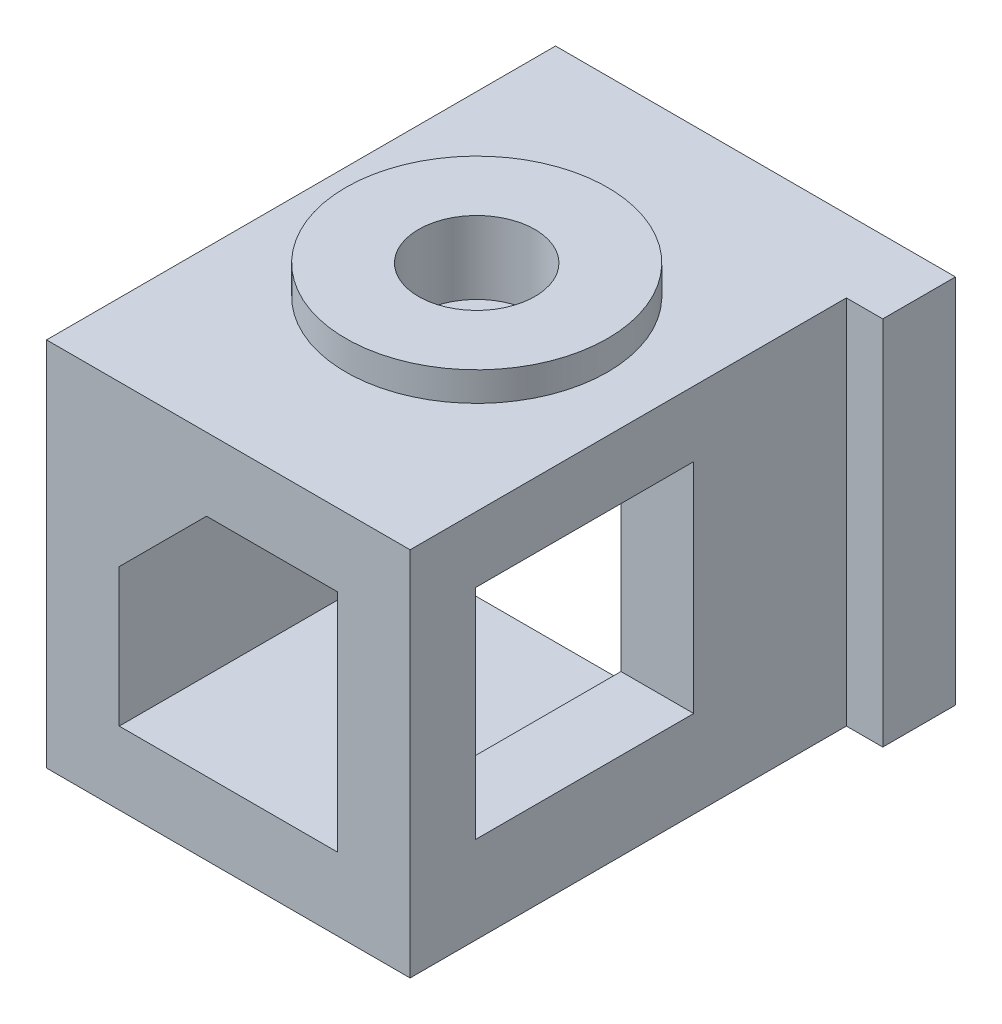
SolidWorks part; units mm, degrees
ref_plane "Front Plane" through (0, 0, 0) normal (0, 0, 1) x (1, 0, 0)
ref_plane "Top Plane" through (0, 0, 0) normal (0, 1, 0) x (1, 0, 0)
ref_plane "Right Plane" through (0, 0, 0) normal (1, 0, 0) x (0, 0, -1)
sketch "Sketch1" plane through (0, 0, 0) normal (0, 0, 1) x (1, 0, 0)
  line L0 (-9.3056, 4.7356) -> (15.6944, 4.7356)
  line L1 (15.6944, 4.7356) -> (15.6944, -0.2644)
  line L2 (15.6944, -0.2644) -> (1.6944, -0.2644)
  line L3 (1.6944, -0.2644) -> (-4.3056, -6.2644)
  line L4 (-4.3056, -6.2644) -> (-4.3056, -13.2644)
  line L5 (-4.3056, -13.2644) -> (-9.3056, -13.2644)
  line L6 (-9.3056, -13.2644) -> (-9.3056, 4.7356)
  line L7 (-4.3056, -6.2644) -> (-4.3056, -0.2644) construction
  line L8 (-4.3056, -0.2644) -> (1.6944, -0.2644) construction
  dimension "D1" = 18
  dimension "D2" = 25
  dimension "D3" = 5
  dimension "D4" = 5
  dimension "D5" = 6
  dimension "D6" = 6
extrude "Boss-Extrude1" add sketch "Sketch1" along normal blind 35
sketch "Sketch2" plane through (0, 4.7356, 0) normal (0, 1, 0) x (1, 0, 0)
  line L0 (-9.3056, -35) -> (-9.3056, 0) construction
  line L1 (15.6944, 0) -> (-9.3056, 0) construction
  circle A0 centre (2.9044, -17.63) radius 9
  dimension "D1" = 18
  dimension "D2" = 12.21
  dimension "D3" = 17.63
extrude "Boss-Extrude2" add sketch "Sketch2" along normal blind 2
sketch "Sketch3" plane through (0, 6.7356, 0) normal (0, 1, 0) x (1, 0, 0)
  circle A0 centre (2.9044, -17.63) radius 4
  dimension "D1" = 8
extrude "Cut-Extrude1" cut sketch "Sketch3" against normal blind 5
sketch "Sketch4" plane through (0, -0.2644, 0) normal (0, -1, 0) x (1, 0, 0)
  line L0 (1.6944, 35) -> (15.6944, 35) construction
  line L1 (15.6944, 35) -> (10.6944, 35)
  line L2 (15.6944, 35) -> (15.6944, 0)
  line L3 (15.6944, 0) -> (10.6944, 0)
  line L4 (10.6944, 35) -> (10.6944, 0)
  line L5 (15.6944, 35) -> (15.6944, 0) construction
  line L6 (1.6944, 0) -> (15.6944, 0) construction
  dimension "D1" = 5
extrude "Boss-Extrude3" add sketch "Sketch4" along normal blind 20.5
sketch "Sketch6" plane through (15.6944, 0, 0) normal (1, 0, 0) x (0, 0, -1)
  line L0 (-35, 4.7356) -> (0, 4.7356) construction
  line L1 (0, -20.7644) -> (-5, -20.7644)
  line L2 (0, -20.7644) -> (0, 4.7356)
  line L3 (0, 4.7356) -> (-5, 4.7356)
  line L4 (-5, -20.7644) -> (-5, 4.7356)
  dimension "D1" = 5
extrude "Boss-Extrude4" add sketch "Sketch6" along normal blind 2.5
sketch "Sketch7" plane through (0, -13.2644, 0) normal (0, -1, 0) x (1, 0, 0)
  line L0 (-4.3056, 35) -> (-4.3056, 0) construction
  line L1 (-9.3056, 35) -> (-4.3056, 35)
  line L2 (-9.3056, 35) -> (-9.3056, 15)
  line L3 (-9.3056, 15) -> (-4.3056, 15)
  line L4 (-4.3056, 35) -> (-4.3056, 15)
  dimension "D1" = 20
extrude "Boss-Extrude5" add sketch "Sketch7" along normal up to surface (7.5 mm away) up to face at (14.8611, -20.7644, 13.3333)
sketch "Sketch8" plane through (-4.3056, 0, 0) normal (1, 0, 0) x (0, 0, -1)
  line L0 (-15, -20.7644) -> (-15, -13.2644) construction
  line L1 (-35, -20.7644) -> (-15, -20.7644)
  line L2 (-35, -20.7644) -> (-35, -15.7644)
  line L3 (-35, -15.7644) -> (-15, -15.7644)
  line L4 (-15, -20.7644) -> (-15, -15.7644)
  dimension "D1" = 5
extrude "Boss-Extrude6" add sketch "Sketch8" along normal up to surface (15 mm away) up to face at (10.6944, -10.5144, 17.5)
sketch "Sketch10" plane through (15.6944, 0, 0) normal (1, 0, 0) x (0, 0, -1)
  line L0 (-35, 4.7356) -> (-5, 4.7356) construction
  line L1 (-30.5, 0.2356) -> (-15.5, 0.2356)
  line L2 (-30.5, 0.2356) -> (-30.5, -14.7644)
  line L3 (-30.5, -14.7644) -> (-15.5, -14.7644)
  line L4 (-15.5, 0.2356) -> (-15.5, -14.7644)
  line L5 (-30.5, 0.2356) -> (-15.5, -14.7644) construction
  line L6 (-30.5, -14.7644) -> (-15.5, 0.2356) construction
  line L7 (-35, -20.7644) -> (-35, 4.7356) construction
  point P0 (-23, -7.2644)
  dimension "D1" = 15
  dimension "D2" = 15
  dimension "D3" = 12
  dimension "D4" = 12
extrude "Cut-Extrude2" cut sketch "Sketch10" against normal up to surface (5 mm away) up to face at (10.6944, -12.2644, 16.6667)
